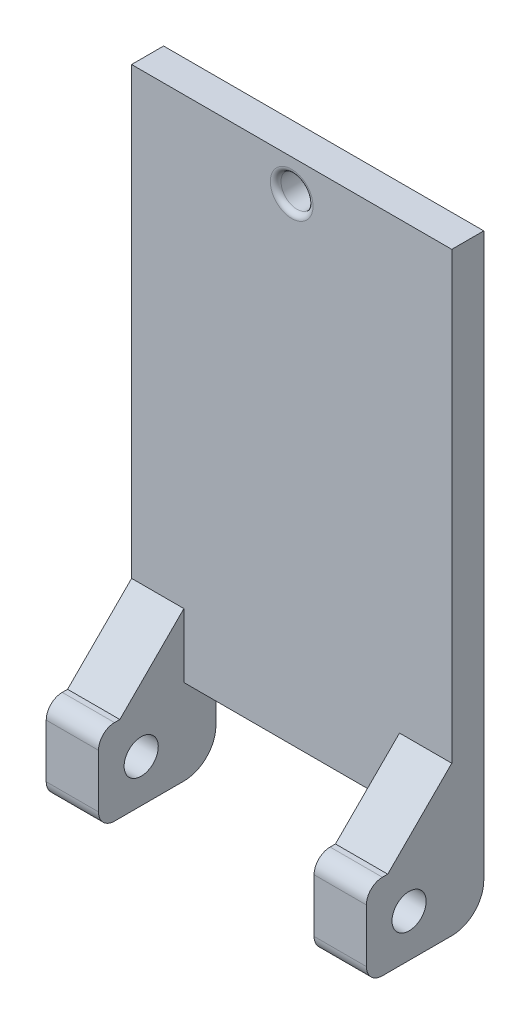
SolidWorks part; units mm, degrees
ref_plane "Front Plane" through (0, 0, 0) normal (0, 0, 1) x (1, 0, 0)
ref_plane "Top Plane" through (0, 0, 0) normal (0, 1, 0) x (1, 0, 0)
ref_plane "Right Plane" through (0, 0, 0) normal (1, 0, 0) x (0, 0, -1)
sketch "Sketch1" plane through (0, 0, 0) normal (0, 0, 1) x (1, 0, 0)
  line L1 (-15, -27.85) -> (15, -27.85)
  line L2 (-15, -27.85) -> (-15, 27.85)
  line L3 (-15, 27.85) -> (15, 27.85)
  line L4 (15, -27.85) -> (15, 27.85)
  line L5 (-15, -27.85) -> (15, 27.85) construction
  line L6 (-15, 27.85) -> (15, -27.85) construction
  point P0 (0, 0)
  dimension "D1" = 55.7
  dimension "D2" = 30
extrude "Boss-Extrude1" add sketch "Sketch1" along normal blind 3
sketch "Sketch2" plane through (0, 0, 3) normal (0, 0, 1) x (1, 0, 0)
  line L0 (0, -27.85) -> (0, 27.85) construction
  line L1 (15, 27.85) -> (-15, 27.85) construction
  line L3 (-15, -27.85) -> (-10.1, -27.85)
  line L4 (-15, -27.85) -> (-15, -19.85)
  line L5 (-15, -19.85) -> (-10.1, -19.85)
  line L6 (-10.1, -27.85) -> (-10.1, -19.85)
  point P6 (0, 0)
  dimension "D1" = 4.9
  dimension "D2" = 8
extrude "Boss-Extrude2" add sketch "Sketch2" along normal blind 8
sketch "Sketch3" plane through (-15, 0, 0) normal (-1, 0, 0) x (0, 0, 1)
  line L0 (11, -27.85) -> (0, -27.85) construction
  line L2 (3, 27.85) -> (3, -19.85) construction
  circle A0 centre (7, -23.85) radius 1.6
  dimension "D1" = 3.2
  dimension "D2" = 4
  dimension "D3" = 4
extrude "Cut-Extrude1" cut sketch "Sketch3" against normal through all
mirror "Mirror1" about plane through (0, 0, 0) normal (1, 0, 0) of "Cut-Extrude1", "Boss-Extrude2"
sketch "Sketch4" plane through (0, 0, 3) normal (0, 0, 1) x (1, 0, 0)
  line L1 (15, 27.85) -> (-15, 27.85) construction
  line L3 (0, 27.85) -> (0, 24.85) construction
  circle A0 centre (0, 24.85) radius 1.5
  dimension "D1" = 3
  dimension "D2" = 3
extrude "Cut-Extrude2" cut sketch "Sketch4" against normal blind 10 contours A0
fillet "Fillet3" radius 0.5 2 edges at (-1.5, 24.85, 0) (1.5, 24.85, 3)
fillet "Fillet4" radius 3 1 edges at (0, -27.85, 0)
sketch "Sketch5" plane through (0, 0, 3) normal (0, 0, 1) x (1, 0, 0)
  line L0 (10.1, -27.85) -> (10.1, -19.85) construction
  line L1 (-10.1, -27.85) -> (-10.1, -19.85) construction
  line L2 (10.1, -27.85) -> (10.1, -19.85)
  line L3 (-10.1, -27.85) -> (-10.1, -19.85)
  line L4 (-10.1, -19.85) -> (10.1, -19.85)
  line L5 (10.1, -27.85) -> (10.1, -30.3306)
  line L6 (10.1, -30.3306) -> (-10.1, -30.3306)
  line L7 (-10.1, -30.3306) -> (-10.1, -27.85)
  line M2 (-10.1, -19.85) -> (-10.1, -27.85)
  line M4 (10.1, -27.85) -> (10.1, -19.85)
extrude "Cut-Extrude4" cut sketch "Sketch5" against normal blind 10 and the other way through all contours L4 M2 M4 | L7 L6 L5 region at (0, -25.0903, 3)
fillet "Fillet5" radius 1.5 4 edges at (12.55, -27.85, 11) (12.55, -19.85, 11) (-12.55, -27.85, 11) (-12.55, -19.85, 11)
chamfer "Chamfer1" distance 6 angle 45 2 edges at (-12.55, -19.85, 3) (12.55, -19.85, 3)
